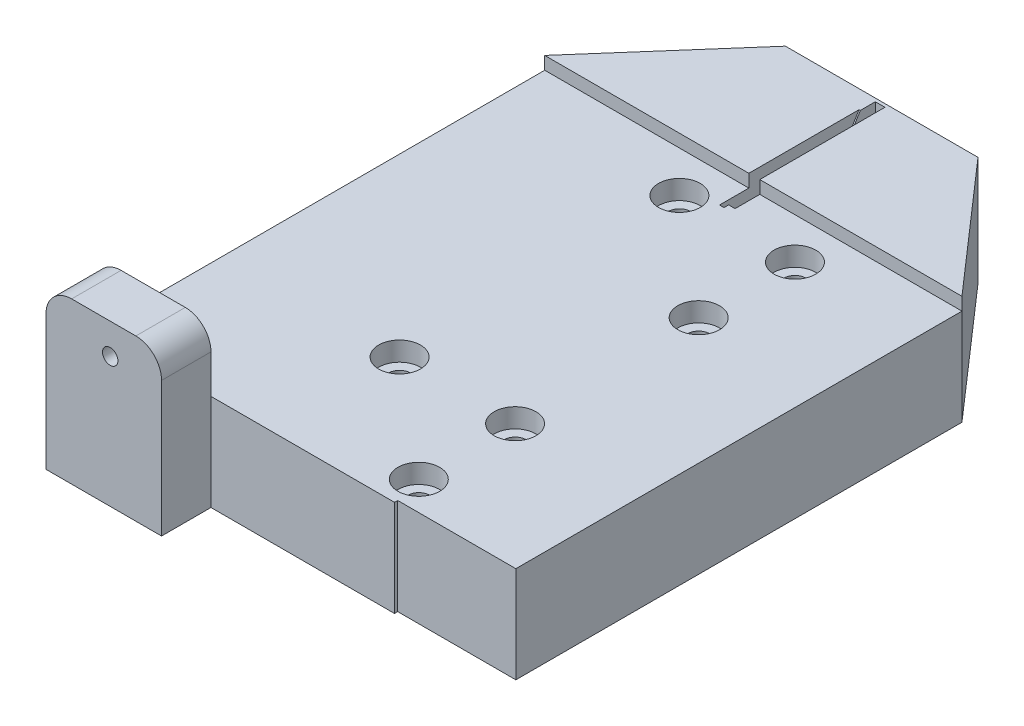
SolidWorks part; units mm, degrees
ref_plane "Front Plane" through (0, 0, 0) normal (0, 0, 1) x (1, 0, 0)
ref_plane "Top Plane" through (0, 0, 0) normal (0, 1, 0) x (1, 0, 0)
ref_plane "Right Plane" through (0, 0, 0) normal (1, 0, 0) x (0, 0, -1)
sketch "Sketch1" plane through (0, 0, 0) normal (0, 1, 0) x (1, 0, 0)
  line L0 (-32.5, 70) -> (-32.5, 0)
  line L1 (-32.5, 70) -> (32.5, 70)
  line L2 (-32.5, 0) -> (32.5, 0)
  line L3 (32.5, 70) -> (32.5, 0)
  line L4 (-32.5, 70) -> (32.5, 0) construction
  line L5 (-32.5, 0) -> (32.5, 70) construction
  line L6 (-32.5, 70) -> (-15, 90)
  line L7 (-15, 90) -> (15, 90)
  line L8 (15, 90) -> (32.5, 70)
  line L10 (-32.5, 0) -> (-14.5, 0)
  line L11 (-32.5, 0) -> (-32.5, -7.7)
  line L12 (-32.5, -7.7) -> (-14.5, -7.7)
  line L13 (-14.5, 0) -> (-14.5, -7.7)
  line L14 (32.5, 0) -> (14.1, 0)
  line L15 (32.5, 0) -> (32.5, 0.5)
  line L16 (32.5, 0.5) -> (14.1, 0.5)
  line L17 (14.1, 0) -> (14.1, 0.5)
  point P1 (0, 35)
  point P2 (0, 0)
  dimension "D1" = 65
  dimension "D2" = 30
  dimension "D3" = 90
  dimension "D4" = 20
  dimension "D5" = 7.7
  dimension "D6" = 18
  dimension "D7" = 0.5
  dimension "D8" = 18.4
extrude "Boss-Extrude1" add sketch "Sketch1" along normal blind 17 contours L3 L1 L0 L2 | L8 L7 L6 L1 | L13 L2 L11 L12 region at (-0.0472, 0, -35.0704) region at (0, 0, -78.7719) region at (-23.5, 0, 3.85)
extrude "Boss-Extrude2" add sketch "Sketch1<3>" along normal blind 8 from surface contours L13 L2 L11 L12 region at (-23.5, 0, 3.85) starting at face at (-0.08, 17, -30.56)
sketch "Sketch1<3>" plane through (0, 0, 0) normal (0, 1, 0) x (1, 0, 0) same geometry as "Sketch1"
sketch "Sketch9" plane through (0, 17, 0) normal (0, 1, 0) x (1, 0, 0)
  line L1 (-32.5, 70) -> (32.5, 70)
  line L2 (-32.5, 70) -> (-32.5, 0)
  line L3 (-32.5, 0) -> (32.5, 0)
  line L4 (32.5, 70) -> (32.5, 0)
  point P4 (32.5, 0)
extrude "Cut-Extrude5" cut sketch "Sketch9" against normal blind 2
sketch "Sketch2" plane through (0, 15, 0) normal (0, 1, 0) x (1, 0, 0)
  line L0 (0, -1000) -> (0, 49000) construction
  line L1 (-32.5, 0) -> (32.5, 0) construction
  line L2 (-5.12, 20) -> (-5.12, 63.6) construction
  point P0 (-5.12, 20)
  point P1 (12.88, 20)
  point P2 (-5.12, 63.6)
  point P3 (12.88, 63.6)
  point P9 (12.88, 5)
  point P11 (12.88, 48.6)
  dimension "D1" = 12.88
  dimension "D2" = 18
  dimension "D3" = 5
  dimension "D4" = 15
  dimension "D6" = 43.6
  dimension "D5" = 2
hole_wizard "CBORE for M3 SHCS2" positions "Sketch2" profile "Sketch10" counterbore size "M3" standard "ANSI Metric" end condition through all
sketch "Sketch10" plane through (-5.12, 15, -20) normal (1, 0, 0) x (0, 0, 1)
  line L0 (0, 0) -> (0, 15)
  line L1 (0, 15) -> (1.7, 15)
  line L3 (1.7, 15) -> (1.7, 3)
  line L4 (1.7, 3) -> (3.25, 3)
  line L5 (3.25, 3) -> (3.25, 0)
  line L7 (3.25, 0) -> (0, 0)
  line L11 (0, -6.35) -> (0, 107.95) construction
  dimension "Thru Hole Dia." = 3.4
  dimension "Thru Hole Depth" = 15
  dimension "C'Bore Dia." = 6.5
  dimension "C'Bore Depth" = 3
sketch "Sketch4" plane through (0, 0, 0) normal (1, 0, 0) x (0, 0, -1)
  line L0 (57.4909, 2) -> (78, 2)
  line L1 (57.4909, 2) -> (68.4909, 20)
  line L2 (78, 2) -> (89, 20)
  line L3 (68.4909, 20) -> (89, 20)
  line L4 (90, 17) -> (70, 17) construction
  line L5 (90, 17) -> (90, 0) construction
  circle A0 centre (78, 2) radius 1
  circle A1 centre (57.4909, 2) radius 1
  dimension "D6" = 2
  dimension "D7" = 2
  dimension "D1" = 18
  dimension "D2" = 11
  dimension "D3" = 17.5
  dimension "D4" = 3
  dimension "D5" = 1
extrude "Cut-Extrude3" cut sketch "Sketch4" against normal blind 0.7 contours L0 A0 L2 | L2 A0 L0 | L1 A1 L0 | L0 A1 L1 | A1 L0 A0 L2 L3 L1 region at (0, 2.3121, -58.0474) region at (0, 1.9394, -57.3828) region at (0, 11.0366, -73.2537) region at (0, 2.4786, -77.7316) region at (0, 1.7564, -78.1366)
sketch "Sketch6" plane through (0, 0, 0) normal (-1, 0, 0) x (0, 0, 1)
  line L0 (-70, 17) -> (-90, 17) construction
  line L1 (-89.5, 17) -> (-66.1576, 17)
  line L2 (-89.5, 17) -> (-89.5, 13)
  line L3 (-89.5, 13) -> (-66.1576, 13)
  line L4 (-66.1576, 17) -> (-66.1576, 13)
  line L5 (-57.4909, 2) -> (-68.4909, 20) construction
  point P6 (-66.6576, 17)
  point P8 (-66.6576, 17)
  dimension "D1" = 0.5
  dimension "D2" = 0.5
  dimension "D3" = 4
extrude "Cut-Extrude4" cut sketch "Sketch6" against normal blind 1 and the other way blind 0.5
sketch "Sketch7" plane through (0, 0, 0) normal (0, 0, -1) x (-1, 0, 0)
  line L0 (32.5, 25) -> (32.5, 15) construction
  line L1 (32.5, 0) -> (15, 0) construction
  point P0 (22.5, 20.24)
  dimension "D1" = 10
  dimension "D2" = 20.24
hole_wizard "CBORE for M2 SHCS1" positions "Sketch7" profile "Sketch8" counterbore size "M2" standard "ANSI Metric" end condition through all
sketch "Sketch8" plane through (-22.5, 20.24, 0) normal (1, 0, 0) x (0, 1, 0)
  line L0 (0, 0) -> (0, 7.7)
  line L1 (0, 7.7) -> (1.2, 7.7)
  line L3 (1.2, 7.7) -> (1.2, 2)
  line L4 (1.2, 2) -> (2.2, 2)
  line L5 (2.2, 2) -> (2.2, 0)
  line L7 (2.2, 0) -> (0, 0)
  line L11 (0, -6.35) -> (0, 107.95) construction
  dimension "Thru Hole Dia." = 2.4
  dimension "Thru Hole Depth" = 7.7
  dimension "C'Bore Dia." = 4.4
  dimension "C'Bore Depth" = 2
fillet "Fillet1" radius 4 2 edges at (-14.5, 25, 3.85) (-32.5, 25, 3.85)
equation "\"D8@Sketch1\"=\"D6@Sketch1\"+0.4"
